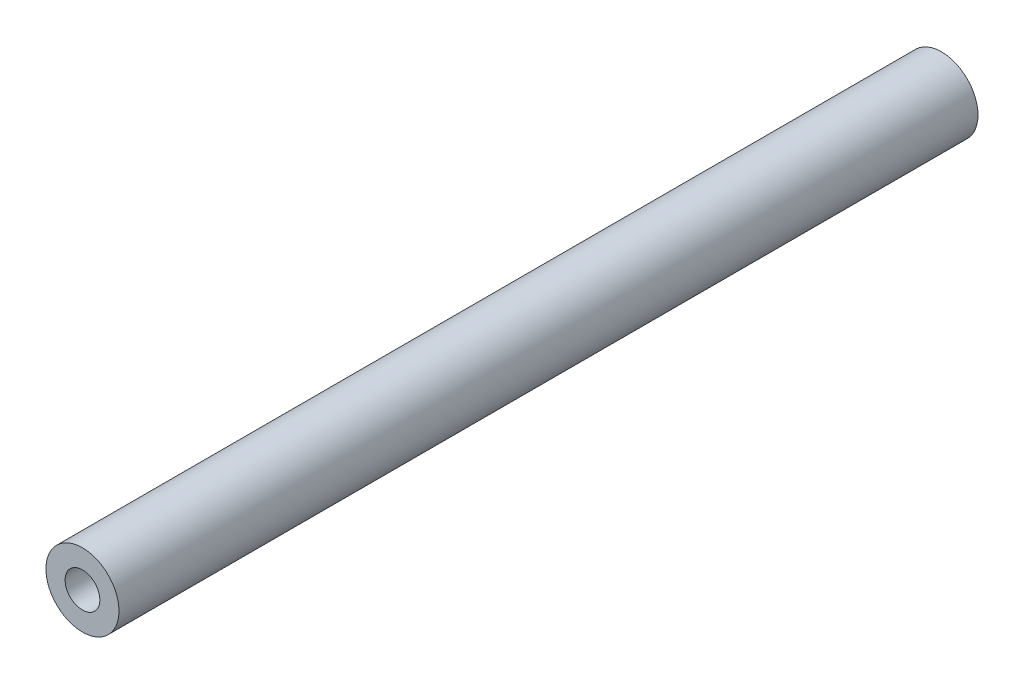
SolidWorks part; units mm, degrees
ref_plane "Plano frontal" through (0, 0, 0) normal (0, 0, 1) x (1, 0, 0)
ref_plane "Plano superior" through (0, 0, 0) normal (0, 1, 0) x (1, 0, 0)
ref_plane "Plano direito" through (0, 0, 0) normal (1, 0, 0) x (0, 0, -1)
sketch "Esboço1" plane through (0, 0, 0) normal (0, 0, 1) x (1, 0, 0)
  circle A0 centre (0, 0) radius 1
  circle A1 centre (0, 0) radius 2.1
  dimension "D1" = 2
  dimension "D2" = 4.2
extrude "Ressalto-extrusão1" add sketch "Esboço1" along normal blind 49.4
ref_axis "Eixo1" through (0, 0, 49.4) along (0, 0, -1)
